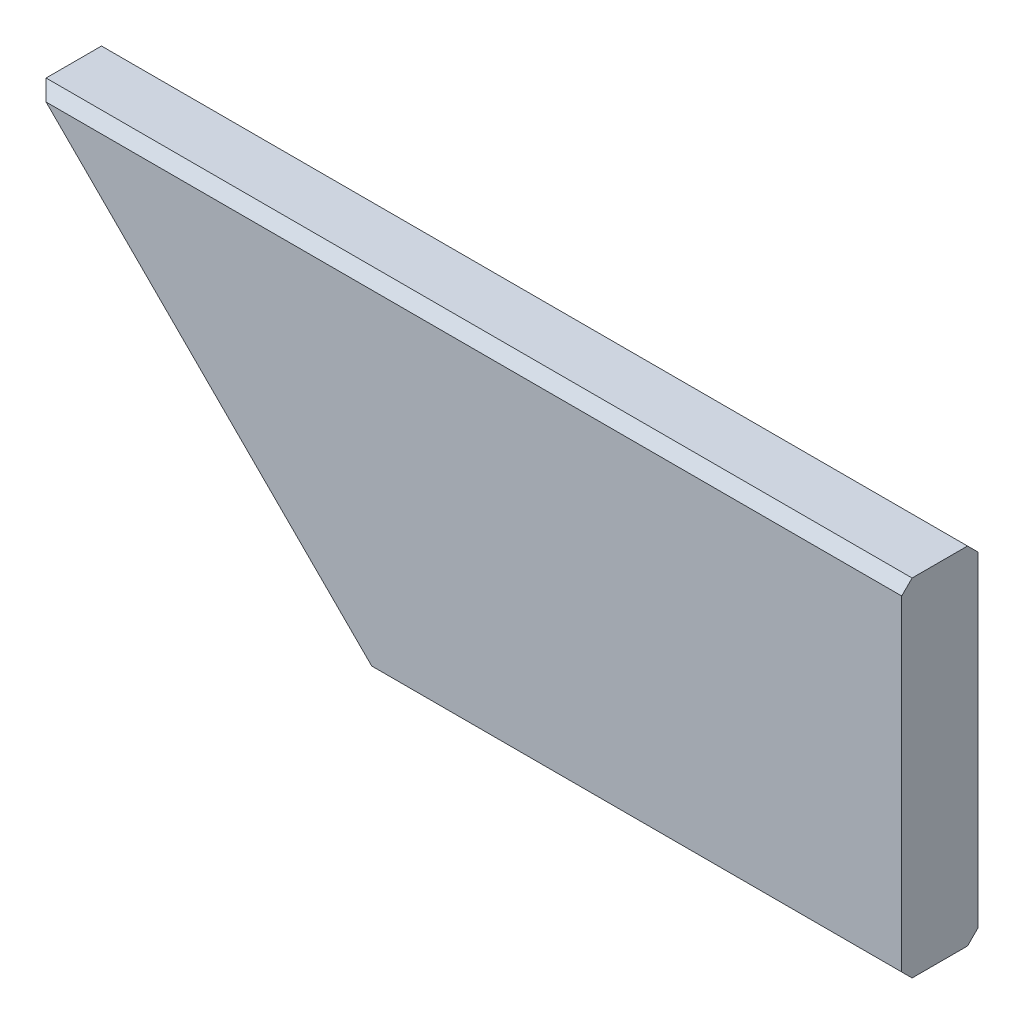
SolidWorks part; units mm, degrees
ref_plane "Plan de face" through (0, 0, 0) normal (0, 0, 1) x (1, 0, 0)
ref_plane "Plan de dessus" through (0, 0, 0) normal (0, 1, 0) x (1, 0, 0)
ref_plane "Plan de droite" through (0, 0, 0) normal (1, 0, 0) x (0, 0, -1)
sketch "Esquisse1" plane through (0, 0, 0) normal (0, 0, 1) x (1, 0, 0)
  line L1 (0, 0) -> (1950, 0)
  line L2 (0, 0) -> (0, 100)
  line L3 (0, 100) -> (1950, 100)
  line L4 (1950, 0) -> (1950, 100)
  dimension "D1" = 1950
  dimension "D2" = 100
extrude "Boss.-Extru.1" add sketch "Esquisse1" along normal blind 22
sketch "Esquisse2" plane through (0, 0, 0) normal (0, 0, -1) x (-1, 0, 0)
  line L0 (0, 0) -> (-750, 0)
  line L1 (0, 0) -> (-1950, 0) construction
  line L2 (-750, 0) -> (-650, 100)
  line L3 (-1950, 100) -> (0, 100) construction
  line L4 (-650, 100) -> (0, 100)
  line L5 (-1950, 0) -> (-1950, 100) construction
  line L6 (0, 0) -> (0, 100)
  dimension "D1" = 45
  dimension "D2" = 1200
extrude "Enlèv. mat.-Extru.1" cut sketch "Esquisse2" against normal through all both and the other way through all
chamfer "Chanfrein1" distance 3 angle 45 4 edges at (1350, 0, 0) (1350, 0, 22) (1300, 100, 0) (1300, 100, 22)
sketch "Esquisse3" plane through (0, 0, 0) normal (0, 0, -1) x (-1, 0, 0)
  line L0 (-1950, 100) -> (-650, 100) construction
  line L1 (-1950, 0) -> (-900, 0)
  line L2 (-1950, 0) -> (-1950, 100)
  line L3 (-1950, 100) -> (-900, 100)
  line L4 (-900, 0) -> (-900, 100)
  dimension "D1" = 1050
extrude "Enlèv. mat.-Extru.2" cut sketch "Esquisse3" against normal through all both and the other way through all
